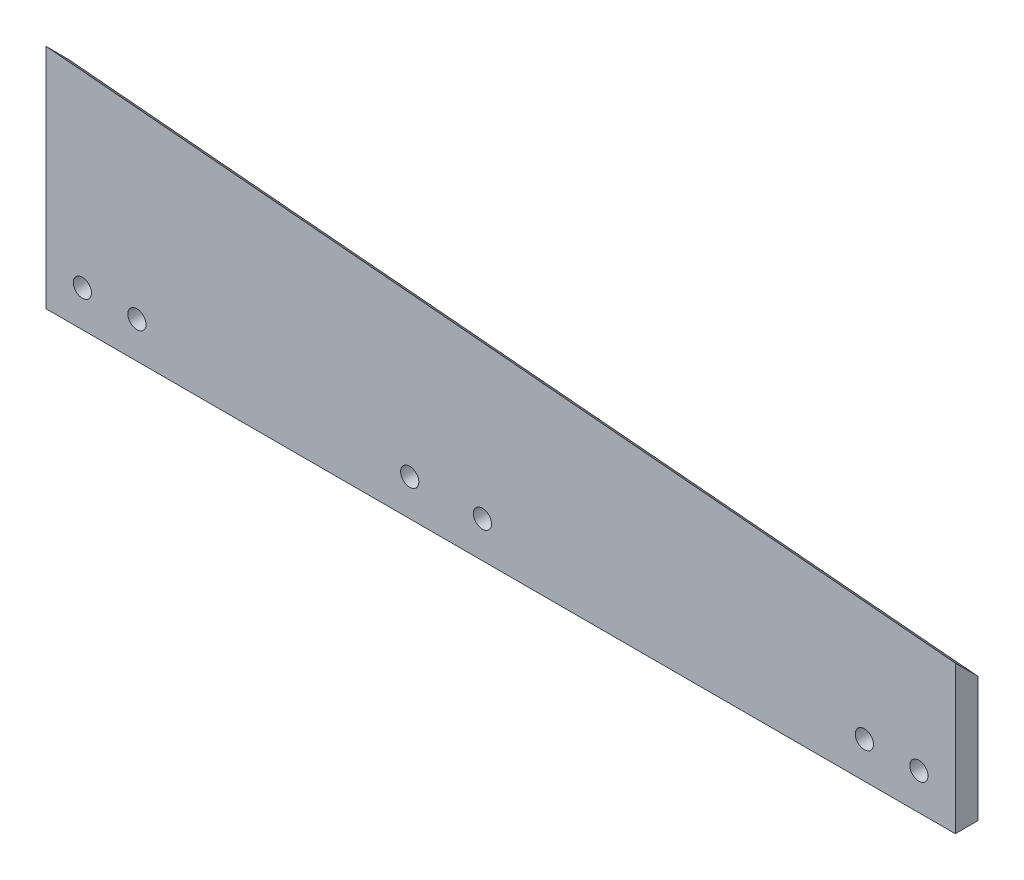
SolidWorks part; units mm, degrees
ref_plane "Front Plane" through (0, 0, 0) normal (0, 0, 1) x (1, 0, 0)
ref_plane "Top Plane" through (0, 0, 0) normal (0, 1, 0) x (1, 0, 0)
ref_plane "Right Plane" through (0, 0, 0) normal (1, 0, 0) x (0, 0, -1)
sketch "Sketch1" plane through (0, 0, 0) normal (1, 0, 0) x (0, 0, -1)
  line L1 (-5, 50) -> (0, 50)
  line L2 (-5, 50) -> (-5, 0)
  line L3 (-5, 0) -> (0, 0)
  line L4 (0, 50) -> (0, 0)
  dimension "D1" = 5
  dimension "D2" = 50
extrude "Boss-Extrude1" add sketch "Sketch1" along normal blind 200
sketch "Sketch3" plane through (0, 0, 5) normal (0, 0, 1) x (1, 0, 0)
  line L0 (0, 50) -> (200, 50)
  line L1 (200, 50) -> (200, 32.5023)
  line L2 (200, 50) -> (200, 0) construction
  line L3 (200, 32.5023) -> (0, 50)
  line L4 (200, 43.0009) -> (80, 43.0009) construction
  dimension "D1" = 5
  dimension "D2" = 120
extrude "Cut-Extrude2" cut sketch "Sketch3" against normal up to surface (5 mm away) up to face at (100, 25, 0)
chamfer "Chamfer1" distance 5 angle 45 1 edges at (100, 41.2511, 0)
sketch "Sketch2" plane through (0, 0, 0) normal (0, 0, -1) x (-1, 0, 0)
  line L1 (-200, 0) -> (0, 0) construction
  line L2 (-200, 0) -> (-200, 27.4832) construction
  circle A0 centre (-192, 8) radius 2
  circle A1 centre (-180, 8) radius 2
  point P8 (-138.6862, -169.2325)
  point P9 (-137.7215, -173.3048)
  dimension "D1" = 4
  dimension "D2" = 8
  dimension "D3" = 8
  dimension "D4" = 12
extrude "Cut-Extrude1" cut sketch "Sketch2" against normal up to surface (5 mm away) up to face at (100, 20.6256, 5)
ref_plane "Plane1" through (100, 0, 0) normal (1, 0, 0) x (0, 0, -1)
mirror "Mirror2" about plane through (100, 0, 0) normal (1, 0, 0) of "Cut-Extrude1"
sketch "Sketch4" plane through (0, 0, 0) normal (0, 0, -1) x (-1, 0, 0)
  line L0 (-200, 0) -> (-200, 27.4832) construction
  circle A2 centre (-80, 8) radius 2
  circle A3 centre (-96, 8) radius 2
  point P4 (0, 0)
  dimension "D1" = 4
  dimension "D3" = 16
  dimension "D2" = 120
extrude "Cut-Extrude3" cut sketch "Sketch4" against normal up to surface (5 mm away) up to face at (8, 10, 5)
